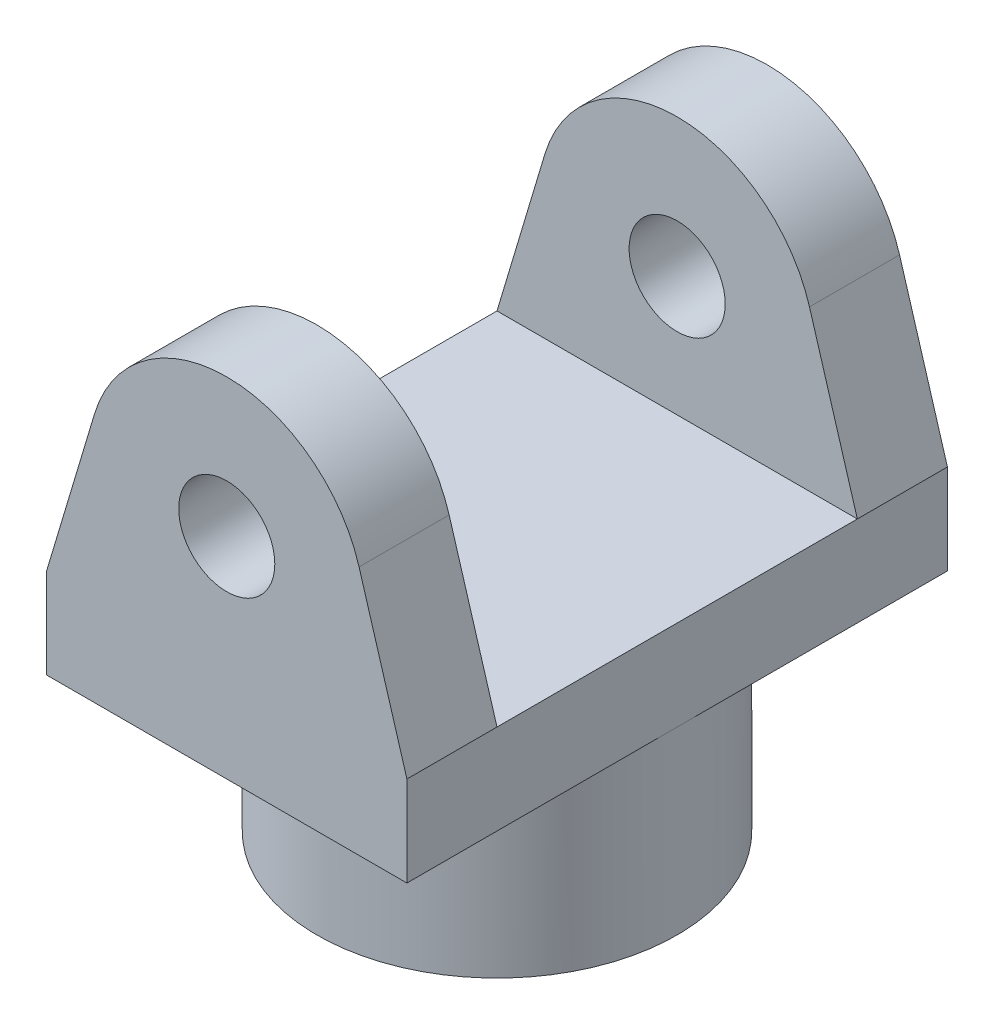
SolidWorks part; units mm, degrees
ref_plane "Front Plane" through (0, 0, 0) normal (0, 0, 1) x (1, 0, 0)
ref_plane "Top Plane" through (0, 0, 0) normal (0, 1, 0) x (1, 0, 0)
ref_plane "Right Plane" through (0, 0, 0) normal (1, 0, 0) x (0, 0, -1)
sketch "Sketch1" plane through (0, 0, 0) normal (0, 0, 1) x (1, 0, 0)
  line L0 (-22.0329, 6.5993) -> (-30, -20)
  line L1 (-30, -20) -> (-30, -35)
  line L2 (-30, -35) -> (30, -35)
  line L3 (0, 0) -> (0, 39.9536) construction
  line L4 (30, -20) -> (30, -35)
  line L5 (22.0329, 6.5993) -> (30, -20)
  line L6 (-30, -20) -> (30, -20)
  circle A0 centre (0, 0) radius 8
  arc A1 (22.0329, 6.5993) -> (-22.0329, 6.5993) centre (0, 0) ccw
  point P10 (0, -35)
  dimension "D1" = 16
  dimension "D2" = 46
  dimension "D3" = 35
  dimension "D4" = 60
  dimension "D5" = 15
extrude "Boss-Extrude1" add sketch "Sketch1" along normal blind 90 contours L6 L1 L2 L4 region at (0, -27.5, 0)
extrude "Boss-Extrude2" add sketch "Sketch1<3>" along normal blind 15 contours A0 A1 L0 L6 L5 region at (0, 22.2618, 0)
sketch "Sketch1<3>" plane through (0, 0, 0) normal (0, 0, 1) x (1, 0, 0) same geometry as "Sketch1"
ref_plane "Plane1" through (0, 0, 45) normal (0, 0, 1) x (1, 0, 0)
mirror "Mirror1" about plane through (0, 0, 45) normal (0, 0, 1) of "Boss-Extrude2"
sketch "Sketch2" plane through (0, -35, 0) normal (0, -1, 0) x (1, 0, 0)
  line L0 (31.9, 45) -> (-31.9, 45) construction
  line L1 (-2, 59.8661) -> (-2, 65.8661)
  line L2 (-2, 65.8661) -> (2, 65.8661)
  line L3 (2, 65.8661) -> (2, 59.8661)
  circle A0 centre (0, 45) radius 30
  arc A1 (-2, 59.8661) -> (2, 59.8661) centre (0, 45) ccw
  point P7 (0, 65.8661)
  dimension "D1" = 60
  dimension "D2" = 30
  dimension "D3" = 6
  dimension "D4" = 4
extrude "Boss-Extrude3" add sketch "Sketch2" along normal blind 30
